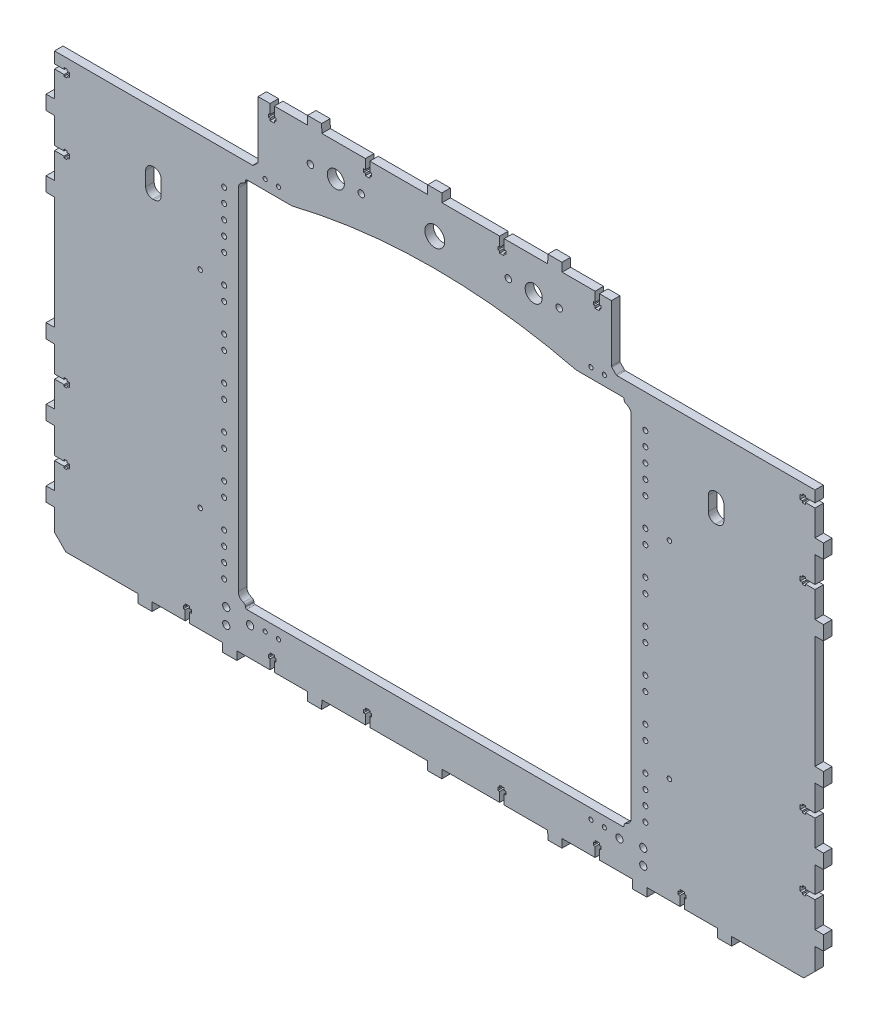
SolidWorks part; units mm, degrees
material "Клен"
ref_plane "Front" through (0, 0, 0) normal (0, 0, 1) x (1, 0, 0)
ref_plane "Top" through (0, 0, 0) normal (0, 1, 0) x (1, 0, 0)
ref_plane "Right" through (0, 0, 0) normal (1, 0, 0) x (0, 0, -1)
sketch "Эскиз1" plane through (0, 0, 0) normal (0, 0, 1) x (1, 0, 0)
  line L0 (1859.5805, 14.5374) -> (1859.5805, 267.5072) construction
  line L1 (1846.6822, 122.5572) -> (1912.7745, 122.5572) construction
  line L2 (1846.6822, 268.5572) -> (1912.7745, 268.5572) construction
  line L3 (1859.5805, 267.5072) -> (1859.5805, 273.1347) construction
  line L6 (1560.5805, 76.7865) -> (1826.5797, 76.7865)
  line L7 (1827.5797, 78.0783) -> (1827.5797, 77.7865)
  line L8 (1832.5805, 332.0072) -> (1832.5797, 84.7865)
  line L9 (1827.5805, 339.0072) -> (1827.5805, 338.7154)
  line L10 (1826.5805, 340.0072) -> (1793.6805, 340.0072)
  line L11 (1560.5805, 340.0072) -> (1592.5638, 340.0072)
  line L13 (1559.5805, 339.0072) -> (1559.5805, 338.7154)
  line L15 (1554.5805, 84.7865) -> (1554.5805, 332.0072)
  line L17 (1559.5805, 78.0783) -> (1559.5805, 77.7865)
  line L18 (1524.5805, 401.0072) -> (1524.5805, 24.1014) construction
  line L19 (1862.5805, 416.6106) -> (1862.5805, 5.7676) construction
  line L20 (1424.5805, 401.0072) -> (1424.5805, 24.1014) construction
  line L21 (1962.5805, 416.6106) -> (1962.5805, 5.7676) construction
  line L22 (1433.5805, 343.0572) -> (1435.0805, 343.0572)
  line L23 (1433.5805, 289.9572) -> (1433.5805, 288.7572)
  line L24 (1433.5805, 149.9572) -> (1433.5805, 148.7572)
  line L25 (1424.5805, 121.4072) -> (1424.5805, 103.0572)
  line L26 (1431.3805, 293.0572) -> (1431.3805, 294.2572)
  line L27 (1431.3805, 154.2572) -> (1433.5805, 154.2572)
  line L28 (1418.5805, 71.5072) -> (1424.5805, 71.4072)
  line L29 (1418.5805, 321.5072) -> (1418.5805, 311.5072)
  line L30 (1418.5805, 311.5072) -> (1424.5805, 311.4072)
  line L31 (1424.5805, 149.9572) -> (1424.5805, 131.6072)
  line L32 (1418.5805, 81.5072) -> (1418.5805, 71.5072)
  line L33 (1433.5805, 338.7572) -> (1431.3805, 338.7572)
  line L34 (1424.5805, 293.0572) -> (1431.3805, 293.0572)
  line L35 (1424.5805, 153.0572) -> (1431.3805, 153.0572)
  line L36 (1433.5805, 103.0572) -> (1435.0805, 103.0572)
  line L37 (1424.5805, 99.9572) -> (1424.5805, 81.6072)
  line L38 (1424.5805, 321.6072) -> (1418.5805, 321.5072)
  line L39 (1433.5805, 293.0572) -> (1435.0805, 293.0572)
  line L40 (1433.5805, 148.7572) -> (1431.3805, 148.7572)
  line L41 (1435.0805, 343.0572) -> (1435.0805, 339.9572)
  line L42 (1431.3805, 289.9572) -> (1424.5805, 289.9572)
  line L43 (1424.5805, 181.6072) -> (1418.5805, 181.5072)
  line L44 (1431.3805, 103.0572) -> (1431.3805, 104.2572)
  line L45 (1435.0805, 103.0572) -> (1435.0805, 99.9572)
  line L46 (1431.3805, 343.0572) -> (1431.3805, 344.2572)
  line L47 (1424.5805, 261.4072) -> (1424.5805, 181.6072)
  line L48 (1433.5805, 153.0572) -> (1435.0805, 153.0572)
  line L49 (1424.5805, 103.0572) -> (1431.3805, 103.0572)
  line L50 (1433.5805, 104.2572) -> (1433.5805, 103.0572)
  line L51 (1424.5805, 311.4072) -> (1424.5805, 293.0572)
  line L52 (1433.5805, 294.2572) -> (1433.5805, 293.0572)
  line L53 (1424.5805, 131.6072) -> (1418.5805, 131.5072)
  line L54 (1431.3805, 338.7572) -> (1431.3805, 339.9572)
  line L55 (1418.5805, 271.5072) -> (1418.5805, 261.5072)
  line L56 (1433.5805, 154.2572) -> (1433.5805, 153.0572)
  line L57 (1433.5805, 98.7572) -> (1431.3805, 98.7572)
  line L58 (1424.5805, 81.6072) -> (1418.5805, 81.5072)
  line L59 (1424.5805, 343.0572) -> (1431.3805, 343.0572)
  line L60 (1431.3805, 339.9572) -> (1424.5805, 339.9572)
  line L61 (1435.0805, 289.9572) -> (1433.5805, 289.9572)
  line L62 (1431.3805, 148.7572) -> (1431.3805, 149.9572)
  line L63 (1435.0805, 339.9572) -> (1433.5805, 339.9572)
  line L64 (1431.3805, 294.2572) -> (1433.5805, 294.2572)
  line L65 (1424.5805, 289.9572) -> (1424.5805, 271.6072)
  line L66 (1433.5805, 99.9572) -> (1433.5805, 98.7572)
  line L67 (1431.3805, 98.7572) -> (1431.3805, 99.9572)
  line L68 (1433.5805, 344.2572) -> (1433.5805, 343.0572)
  line L69 (1424.5805, 271.6072) -> (1418.5805, 271.5072)
  line L70 (1435.0805, 153.0572) -> (1435.0805, 149.9572)
  line L71 (1424.5805, 71.4072) -> (1424.5805, 56.0072)
  line L72 (1431.3805, 344.2572) -> (1433.5805, 344.2572)
  line L73 (1435.0805, 293.0572) -> (1435.0805, 289.9572)
  line L74 (1433.5805, 288.7572) -> (1431.3805, 288.7572)
  line L75 (1418.5805, 131.5072) -> (1418.5805, 121.5072)
  line L76 (1435.0805, 99.9572) -> (1433.5805, 99.9572)
  line L77 (1424.5805, 351.0072) -> (1424.5805, 343.0572)
  line L78 (1418.5805, 171.5072) -> (1424.5805, 171.4072)
  line L79 (1418.5805, 121.5072) -> (1424.5805, 121.4072)
  line L80 (1431.3805, 104.2572) -> (1433.5805, 104.2572)
  line L81 (1431.3805, 288.7572) -> (1431.3805, 289.9572)
  line L82 (1424.5805, 171.4072) -> (1424.5805, 153.0572)
  line L83 (1431.3805, 149.9572) -> (1424.5805, 149.9572)
  line L84 (1433.5805, 339.9572) -> (1433.5805, 338.7572)
  line L85 (1418.5805, 261.5072) -> (1424.5805, 261.4072)
  line L86 (1418.5805, 181.5072) -> (1418.5805, 171.5072)
  line L87 (1431.3805, 99.9572) -> (1424.5805, 99.9572)
  line L88 (1424.5805, 339.9572) -> (1424.5805, 321.6072)
  line L89 (1431.3805, 153.0572) -> (1431.3805, 154.2572)
  line L90 (1435.0805, 149.9572) -> (1433.5805, 149.9572)
  line L91 (1424.5805, 56.0072) -> (1432.5805, 48.0072)
  line L92 (1424.5805, 351.0072) -> (1524.5805, 351.0072)
  line L93 (1432.5805, 48.0072) -> (1483.4805, 48.0072)
  line L94 (1953.5805, 99.9572) -> (1952.0805, 99.9572)
  line L95 (1955.7805, 154.2572) -> (1955.7805, 153.0572)
  line L96 (1953.5805, 289.9572) -> (1952.0805, 289.9572)
  line L97 (1953.5805, 343.0572) -> (1953.5805, 344.2572)
  line L98 (1962.5805, 99.9572) -> (1955.7805, 99.9572)
  line L99 (1955.7805, 153.0572) -> (1962.5805, 153.0572)
  line L100 (1953.5805, 294.2572) -> (1955.7805, 294.2572)
  line L101 (1955.7805, 338.7572) -> (1953.5805, 338.7572)
  line L102 (1953.5805, 103.0572) -> (1953.5805, 104.2572)
  line L103 (1952.0805, 153.0572) -> (1953.5805, 153.0572)
  line L104 (1955.7805, 288.7572) -> (1953.5805, 288.7572)
  line L105 (1962.5805, 321.6072) -> (1962.5805, 339.9572)
  line L106 (1955.7805, 344.2572) -> (1955.7805, 343.0572)
  line L107 (1968.5805, 131.5072) -> (1962.5805, 131.6072)
  line L108 (1962.5805, 149.9572) -> (1955.7805, 149.9572)
  line L109 (1968.5805, 261.5072) -> (1968.5805, 271.5072)
  line L110 (1962.5805, 289.9572) -> (1955.7805, 289.9572)
  line L111 (1955.7805, 343.0572) -> (1962.5805, 343.0572)
  line L112 (1952.0805, 99.9572) -> (1952.0805, 103.0572)
  line L113 (1955.7805, 149.9572) -> (1955.7805, 148.7572)
  line L114 (1952.0805, 293.0572) -> (1953.5805, 293.0572)
  line L115 (1953.5805, 339.9572) -> (1952.0805, 339.9572)
  line L116 (1962.5805, 56.0072) -> (1962.5805, 71.4072)
  line L117 (1955.7805, 103.0572) -> (1962.5805, 103.0572)
  line L118 (1968.5805, 181.5072) -> (1962.5805, 181.6072)
  line L119 (1955.7805, 293.0572) -> (1962.5805, 293.0572)
  line L120 (1953.5805, 344.2572) -> (1955.7805, 344.2572)
  line L121 (1962.5805, 71.4072) -> (1968.5805, 71.5072)
  line L122 (1962.5805, 131.6072) -> (1962.5805, 149.9572)
  line L123 (1968.5805, 171.5072) -> (1968.5805, 181.5072)
  line L124 (1968.5805, 271.5072) -> (1962.5805, 271.6072)
  line L125 (1953.5805, 104.2572) -> (1955.7805, 104.2572)
  line L126 (1953.5805, 153.0572) -> (1953.5805, 154.2572)
  line L127 (1953.5805, 293.0572) -> (1953.5805, 294.2572)
  line L128 (1953.5805, 98.7572) -> (1953.5805, 99.9572)
  line L129 (1962.5805, 121.4072) -> (1968.5805, 121.5072)
  line L130 (1962.5805, 261.4072) -> (1968.5805, 261.5072)
  line L131 (1952.0805, 289.9572) -> (1952.0805, 293.0572)
  line L132 (1952.0805, 343.0572) -> (1953.5805, 343.0572)
  line L133 (1968.5805, 81.5072) -> (1962.5805, 81.6072)
  line L134 (1955.7805, 148.7572) -> (1953.5805, 148.7572)
  line L135 (1962.5805, 293.0572) -> (1962.5805, 311.4072)
  line L136 (1952.0805, 339.9572) -> (1952.0805, 343.0572)
  line L137 (1955.7805, 98.7572) -> (1953.5805, 98.7572)
  line L138 (1962.5805, 103.0572) -> (1962.5805, 121.4072)
  line L139 (1962.5805, 181.6072) -> (1962.5805, 261.4072)
  line L140 (1962.5805, 311.4072) -> (1968.5805, 311.5072)
  line L141 (1952.0805, 103.0572) -> (1953.5805, 103.0572)
  line L142 (1955.7805, 294.2572) -> (1955.7805, 293.0572)
  line L143 (1962.5805, 339.9572) -> (1955.7805, 339.9572)
  line L144 (1955.7805, 104.2572) -> (1955.7805, 103.0572)
  line L145 (1953.5805, 154.2572) -> (1955.7805, 154.2572)
  line L146 (1955.7805, 289.9572) -> (1955.7805, 288.7572)
  line L147 (1968.5805, 121.5072) -> (1968.5805, 131.5072)
  line L148 (1953.5805, 288.7572) -> (1953.5805, 289.9572)
  line L149 (1955.7805, 339.9572) -> (1955.7805, 338.7572)
  line L150 (1954.5805, 48.0072) -> (1962.5805, 56.0072)
  line L151 (1962.5805, 81.6072) -> (1962.5805, 99.9572)
  line L152 (1953.5805, 149.9572) -> (1952.0805, 149.9572)
  line L153 (1962.5805, 171.4072) -> (1968.5805, 171.5072)
  line L154 (1968.5805, 311.5072) -> (1968.5805, 321.5072)
  line L155 (1955.7805, 99.9572) -> (1955.7805, 98.7572)
  line L156 (1952.0805, 149.9572) -> (1952.0805, 153.0572)
  line L157 (1962.5805, 271.6072) -> (1962.5805, 289.9572)
  line L158 (1968.5805, 321.5072) -> (1962.5805, 321.6072)
  line L159 (1962.5805, 343.0572) -> (1962.5805, 351.0072)
  line L160 (1968.5805, 71.5072) -> (1968.5805, 81.5072)
  line L161 (1953.5805, 148.7572) -> (1953.5805, 149.9572)
  line L162 (1962.5805, 153.0572) -> (1962.5805, 171.4072)
  line L163 (1953.5805, 338.7572) -> (1953.5805, 339.9572)
  line L164 (1862.5805, 351.0072) -> (1962.5805, 351.0072)
  line L165 (1954.5805, 48.0072) -> (1903.6805, 48.0072)
  line L166 (1325.5433, 339.9572) -> (1983.9894, 339.9572) construction
  line L167 (1983.9894, 304.9572) -> (1788.8393, 304.9572) construction
  line L168 (1892.5805, 416.6106) -> (1892.5805, 273.8352) construction
  line L169 (1693.5805, 412.8647) -> (1693.5805, 297.5072) construction
  line L170 (1892.0805, 314.9572) -> (1893.0805, 314.9572)
  line L171 (1887.0805, 309.9572) -> (1887.0805, 299.9572)
  line L172 (1892.0805, 294.9572) -> (1893.0805, 294.9572)
  line L173 (1898.0805, 309.9572) -> (1898.0805, 299.9572)
  line L174 (1887.0805, 314.9572) -> (1898.0805, 294.9572) construction
  line L175 (1887.0805, 294.9572) -> (1898.0805, 314.9572) construction
  line L176 (1495.0805, 294.9572) -> (1494.0805, 294.9572)
  line L177 (1489.0805, 309.9572) -> (1489.0805, 299.9572)
  line L178 (1495.0805, 314.9572) -> (1494.0805, 314.9572)
  line L179 (1500.0805, 309.9572) -> (1500.0805, 299.9572)
  line L180 (1893.4805, 48.0072) -> (1893.5805, 42.0072)
  line L181 (1867.0305, 58.5072) -> (1870.1305, 58.5072)
  line L182 (1903.5805, 42.0072) -> (1903.6805, 48.0072)
  line L183 (1867.0305, 54.8072) -> (1865.8305, 54.8072)
  line L184 (1870.1305, 58.5072) -> (1870.1305, 57.0072)
  line L185 (1871.3305, 54.8072) -> (1870.1305, 54.8072)
  line L186 (1865.8305, 57.0072) -> (1867.0305, 57.0072)
  line L187 (1871.3305, 57.0072) -> (1871.3305, 54.8072)
  line L188 (1867.0305, 48.0072) -> (1867.0305, 54.8072)
  line L189 (1870.1305, 57.0072) -> (1871.3305, 57.0072)
  line L190 (1870.1305, 54.8072) -> (1870.1305, 48.0072)
  line L192 (1865.8305, 54.8072) -> (1865.8305, 57.0072)
  line L193 (1893.5805, 42.0072) -> (1903.5805, 42.0072)
  line L194 (1867.0305, 57.0072) -> (1867.0305, 58.5072)
  line L195 (1867.0305, 48.0072) -> (1854.5805, 48.0072)
  line L196 (1893.4805, 48.0072) -> (1870.1305, 48.0072)
  line L197 (1493.5805, 42.0072) -> (1493.6805, 48.0072)
  line L198 (1521.3305, 57.0072) -> (1521.3305, 54.8072)
  line L199 (1517.0305, 48.0072) -> (1517.0305, 54.8072)
  line L200 (1483.5805, 42.0072) -> (1493.5805, 42.0072)
  line L201 (1515.8305, 57.0072) -> (1517.0305, 57.0072)
  line L202 (1521.3305, 54.8072) -> (1520.1305, 54.8072)
  line L203 (1483.4805, 48.0072) -> (1483.5805, 42.0072)
  line L204 (1517.0305, 57.0072) -> (1517.0305, 58.5072)
  line L205 (1517.0305, 58.5072) -> (1520.1305, 58.5072)
  line L206 (1517.0305, 54.8072) -> (1515.8305, 54.8072)
  line L207 (1520.1305, 54.8072) -> (1520.1305, 48.0072)
  line L209 (1520.1305, 58.5072) -> (1520.1305, 57.0072)
  line L210 (1520.1305, 57.0072) -> (1521.3305, 57.0072)
  line L211 (1515.8305, 54.8072) -> (1515.8305, 57.0072)
  line L212 (1520.1305, 48.0072) -> (1532.5805, 48.0072)
  line L213 (1493.6805, 48.0072) -> (1517.0305, 48.0072)
  line L552 (1568.2876, 354.2143) -> (1565.3733, 351.3001)
  line L553 (1564.6662, 351.0072) -> (1524.5805, 351.0072)
  line L624 (1532.5805, 48.0072) -> (1543.4805, 48.0072)
  line L625 (1543.4805, 48.0072) -> (1543.5805, 42.0072)
  line L626 (1543.5805, 42.0072) -> (1553.5805, 42.0072)
  line L627 (1553.5805, 42.0072) -> (1553.6805, 48.0072)
  line L628 (1553.6805, 48.0072) -> (1577.0305, 48.0072)
  line L629 (1577.0305, 48.0072) -> (1577.0305, 54.8072)
  line L630 (1577.0305, 54.8072) -> (1575.8305, 54.8072)
  line L631 (1575.8305, 54.8072) -> (1575.8305, 57.0072)
  line L632 (1575.8305, 57.0072) -> (1577.0305, 57.0072)
  line L633 (1577.0305, 57.0072) -> (1577.0305, 58.5072)
  line L634 (1577.0305, 58.5072) -> (1580.1305, 58.5072)
  line L635 (1580.1305, 58.5072) -> (1580.1305, 57.0072)
  line L636 (1580.1305, 57.0072) -> (1581.3305, 57.0072)
  line L637 (1581.3305, 57.0072) -> (1581.3305, 54.8072)
  line L638 (1581.3305, 54.8072) -> (1580.1305, 54.8072)
  line L639 (1580.1305, 54.8072) -> (1580.1305, 48.0072)
  line L640 (1580.1305, 48.0072) -> (1603.4805, 48.0072)
  line L641 (1603.4805, 48.0072) -> (1603.5805, 42.0072)
  line L642 (1603.5805, 42.0072) -> (1613.5805, 42.0072)
  line L643 (1613.5805, 42.0072) -> (1613.6805, 48.0072)
  line L644 (1613.6805, 48.0072) -> (1644.5305, 48.0072)
  line L645 (1644.5305, 48.0072) -> (1644.5305, 54.8072)
  line L646 (1644.5305, 54.8072) -> (1643.3305, 54.8072)
  line L647 (1643.3305, 54.8072) -> (1643.3305, 57.0072)
  line L648 (1643.3305, 57.0072) -> (1644.5305, 57.0072)
  line L649 (1644.5305, 57.0072) -> (1644.5305, 58.5072)
  line L650 (1644.5305, 58.5072) -> (1647.6305, 58.5072)
  line L651 (1647.6305, 58.5072) -> (1647.6305, 57.0072)
  line L652 (1647.6305, 57.0072) -> (1648.8305, 57.0072)
  line L653 (1648.8305, 57.0072) -> (1648.8305, 54.8072)
  line L654 (1648.8305, 54.8072) -> (1647.6305, 54.8072)
  line L655 (1647.6305, 54.8072) -> (1647.6305, 48.0072)
  line L656 (1647.6305, 48.0072) -> (1688.4805, 48.0072)
  line L657 (1688.4805, 48.0072) -> (1688.5805, 42.0072)
  line L658 (1688.5805, 42.0072) -> (1698.5805, 42.0072)
  line L659 (1698.5805, 42.0072) -> (1698.6805, 48.0072)
  line L660 (1698.6805, 48.0072) -> (1739.5305, 48.0072)
  line L661 (1739.5305, 48.0072) -> (1739.5305, 54.8072)
  line L662 (1739.5305, 54.8072) -> (1738.3305, 54.8072)
  line L663 (1738.3305, 54.8072) -> (1738.3305, 57.0072)
  line L664 (1738.3305, 57.0072) -> (1739.5305, 57.0072)
  line L665 (1739.5305, 57.0072) -> (1739.5305, 58.5072)
  line L666 (1739.5305, 58.5072) -> (1742.6305, 58.5072)
  line L667 (1742.6305, 58.5072) -> (1742.6305, 57.0072)
  line L668 (1742.6305, 57.0072) -> (1743.8305, 57.0072)
  line L669 (1743.8305, 57.0072) -> (1743.8305, 54.8072)
  line L670 (1743.8305, 54.8072) -> (1742.6305, 54.8072)
  line L671 (1742.6305, 54.8072) -> (1742.6305, 48.0072)
  line L672 (1742.6305, 48.0072) -> (1773.4805, 48.0072)
  line L673 (1773.4805, 48.0072) -> (1773.5805, 42.0072)
  line L674 (1773.5805, 42.0072) -> (1783.5805, 42.0072)
  line L675 (1783.5805, 42.0072) -> (1783.6805, 48.0072)
  line L676 (1783.6805, 48.0072) -> (1807.0305, 48.0072)
  line L677 (1807.0305, 48.0072) -> (1807.0305, 54.8072)
  line L678 (1807.0305, 54.8072) -> (1805.8305, 54.8072)
  line L679 (1805.8305, 54.8072) -> (1805.8305, 57.0072)
  line L680 (1805.8305, 57.0072) -> (1807.0305, 57.0072)
  line L681 (1807.0305, 57.0072) -> (1807.0305, 58.5072)
  line L682 (1807.0305, 58.5072) -> (1810.1305, 58.5072)
  line L683 (1810.1305, 58.5072) -> (1810.1305, 57.0072)
  line L684 (1810.1305, 57.0072) -> (1811.3305, 57.0072)
  line L685 (1811.3305, 57.0072) -> (1811.3305, 54.8072)
  line L686 (1811.3305, 54.8072) -> (1810.1305, 54.8072)
  line L687 (1810.1305, 54.8072) -> (1810.1305, 48.0072)
  line L688 (1810.1305, 48.0072) -> (1833.4805, 48.0072)
  line L689 (1833.4805, 48.0072) -> (1833.5805, 42.0072)
  line L690 (1833.5805, 42.0072) -> (1843.5805, 42.0072)
  line L691 (1843.5805, 42.0072) -> (1843.6805, 48.0072)
  line L692 (1843.6805, 48.0072) -> (1854.5805, 48.0072)
  line L763 (1862.5805, 351.0072) -> (1822.4947, 351.0072)
  line L764 (1821.7876, 351.3001) -> (1818.8733, 354.2143)
  line L765 (1818.5805, 354.9215) -> (1818.5805, 395.0072)
  line L766 (1818.5805, 395.0072) -> (1810.1305, 395.0072)
  line L767 (1810.1305, 395.0072) -> (1810.1305, 388.2072)
  line L768 (1810.1305, 388.2072) -> (1811.3305, 388.2072)
  line L769 (1811.3305, 388.2072) -> (1811.3305, 386.0072)
  line L770 (1811.3305, 386.0072) -> (1810.1305, 386.0072)
  line L771 (1810.1305, 386.0072) -> (1810.1305, 384.5072)
  line L772 (1810.1305, 384.5072) -> (1807.0305, 384.5072)
  line L773 (1807.0305, 384.5072) -> (1807.0305, 386.0072)
  line L774 (1807.0305, 386.0072) -> (1805.8305, 386.0072)
  line L775 (1805.8305, 386.0072) -> (1805.8305, 388.2072)
  line L776 (1805.8305, 388.2072) -> (1807.0305, 388.2072)
  line L777 (1807.0305, 388.2072) -> (1807.0305, 395.0072)
  line L778 (1807.0305, 395.0072) -> (1783.6805, 395.0072)
  line L779 (1783.6805, 395.0072) -> (1783.5805, 401.0072)
  line L780 (1783.5805, 401.0072) -> (1773.5805, 401.0072)
  line L781 (1773.5805, 401.0072) -> (1773.4805, 395.0072)
  line L782 (1773.4805, 395.0072) -> (1742.6305, 395.0072)
  line L783 (1742.6305, 395.0072) -> (1742.6305, 388.2072)
  line L784 (1742.6305, 388.2072) -> (1743.8305, 388.2072)
  line L785 (1743.8305, 388.2072) -> (1743.8305, 386.0072)
  line L786 (1743.8305, 386.0072) -> (1742.6305, 386.0072)
  line L787 (1742.6305, 386.0072) -> (1742.6305, 384.5072)
  line L788 (1742.6305, 384.5072) -> (1739.5305, 384.5072)
  line L789 (1739.5305, 384.5072) -> (1739.5305, 386.0072)
  line L790 (1739.5305, 386.0072) -> (1738.3305, 386.0072)
  line L791 (1738.3305, 386.0072) -> (1738.3305, 388.2072)
  line L792 (1738.3305, 388.2072) -> (1739.5305, 388.2072)
  line L793 (1739.5305, 388.2072) -> (1739.5305, 395.0072)
  line L794 (1739.5305, 395.0072) -> (1698.6805, 395.0072)
  line L795 (1698.6805, 395.0072) -> (1698.5805, 401.0072)
  line L796 (1698.5805, 401.0072) -> (1688.5805, 401.0072)
  line L797 (1688.5805, 401.0072) -> (1688.4805, 395.0072)
  line L798 (1688.4805, 395.0072) -> (1647.6305, 395.0072)
  line L799 (1647.6305, 395.0072) -> (1647.6305, 388.2072)
  line L800 (1647.6305, 388.2072) -> (1648.8305, 388.2072)
  line L801 (1648.8305, 388.2072) -> (1648.8305, 386.0072)
  line L802 (1648.8305, 386.0072) -> (1647.6305, 386.0072)
  line L803 (1647.6305, 386.0072) -> (1647.6305, 384.5072)
  line L804 (1647.6305, 384.5072) -> (1644.5305, 384.5072)
  line L805 (1644.5305, 384.5072) -> (1644.5305, 386.0072)
  line L806 (1644.5305, 386.0072) -> (1643.3305, 386.0072)
  line L807 (1643.3305, 386.0072) -> (1643.3305, 388.2072)
  line L808 (1643.3305, 388.2072) -> (1644.5305, 388.2072)
  line L809 (1644.5305, 388.2072) -> (1644.5305, 395.0072)
  line L810 (1644.5305, 395.0072) -> (1613.6805, 395.0072)
  line L811 (1613.6805, 395.0072) -> (1613.5805, 401.0072)
  line L812 (1613.5805, 401.0072) -> (1603.5805, 401.0072)
  line L813 (1603.5805, 401.0072) -> (1603.4805, 395.0072)
  line L814 (1603.4805, 395.0072) -> (1580.1305, 395.0072)
  line L815 (1580.1305, 395.0072) -> (1580.1305, 388.2072)
  line L816 (1580.1305, 388.2072) -> (1581.3305, 388.2072)
  line L817 (1581.3305, 388.2072) -> (1581.3305, 386.0072)
  line L818 (1581.3305, 386.0072) -> (1580.1305, 386.0072)
  line L819 (1580.1305, 386.0072) -> (1580.1305, 384.5072)
  line L820 (1580.1305, 384.5072) -> (1577.0305, 384.5072)
  line L821 (1577.0305, 384.5072) -> (1577.0305, 386.0072)
  line L822 (1577.0305, 386.0072) -> (1575.8305, 386.0072)
  line L823 (1575.8305, 386.0072) -> (1575.8305, 388.2072)
  line L824 (1575.8305, 388.2072) -> (1577.0305, 388.2072)
  line L825 (1577.0305, 388.2072) -> (1577.0305, 395.0072)
  line L826 (1577.0305, 395.0072) -> (1568.5805, 395.0072)
  line L827 (1568.5805, 395.0072) -> (1568.5805, 354.9215)
  circle A0 centre (1859.5805, 268.5572) radius 1.6
  circle A1 centre (1859.5805, 122.5572) radius 1.6
  circle A2 centre (1527.5805, 268.5572) radius 1.6
  circle A3 centre (1527.5805, 122.5572) radius 1.6
  arc A4 (1893.0805, 294.9572) -> (1898.0805, 299.9572) centre (1893.0805, 299.9572) ccw
  arc A5 (1887.0805, 299.9572) -> (1892.0805, 294.9572) centre (1892.0805, 299.9572) ccw
  arc A6 (1893.0805, 314.9572) -> (1898.0805, 309.9572) centre (1893.0805, 309.9572) cw
  arc A7 (1892.0805, 314.9572) -> (1887.0805, 309.9572) centre (1892.0805, 309.9572) ccw
  arc A8 (1568.2876, 354.2143) -> (1568.5805, 354.9215) centre (1567.5805, 354.9215) ccw
  arc A9 (1564.6662, 351.0072) -> (1565.3733, 351.3001) centre (1564.6662, 352.0072) ccw
  arc A10 (1821.7876, 351.3001) -> (1822.4947, 351.0072) centre (1822.4947, 352.0072) ccw
  arc A11 (1818.5805, 354.9215) -> (1818.8733, 354.2143) centre (1819.5805, 354.9215) ccw
  circle A28 centre (1544.5805, 177.5072) radius 1.75
  circle A29 centre (1544.5805, 147.5072) radius 1.75
  circle A30 centre (1544.5805, 137.5072) radius 1.75
  circle A31 centre (1544.5805, 117.5072) radius 1.75
  circle A32 centre (1544.5805, 107.5072) radius 1.75
  circle A33 centre (1544.5805, 97.5072) radius 1.75
  circle A34 centre (1544.5805, 87.5072) radius 1.75
  circle A35 centre (1546.0805, 71.0072) radius 2.55
  circle A36 centre (1546.0805, 60.0072) radius 2.55
  circle A37 centre (1544.5805, 197.5072) radius 1.75
  circle A38 centre (1544.5805, 207.5072) radius 1.75
  circle A39 centre (1544.5805, 227.5072) radius 1.75
  circle A40 centre (1544.5805, 237.5072) radius 1.75
  circle A41 centre (1544.5805, 257.5072) radius 1.75
  circle A42 centre (1544.5805, 267.5072) radius 1.75
  circle A43 centre (1544.5805, 287.5072) radius 1.75
  circle A44 centre (1544.5805, 297.5072) radius 1.75
  circle A45 centre (1544.5805, 307.5072) radius 1.75
  circle A46 centre (1544.5805, 317.5072) radius 1.75
  circle A47 centre (1544.5805, 327.5072) radius 1.75
  circle A87 centre (1573.5805, 347.0072) radius 1.5
  circle A88 centre (1583.0805, 347.0072) radius 1.5
  circle A89 centre (1605.5805, 372.0072) radius 2.3
  circle A90 centre (1623.5805, 372.0072) radius 6.05
  circle A91 centre (1641.5805, 372.0072) radius 2.3
  circle A92 centre (1693.5805, 372.0072) radius 7
  circle A93 centre (1745.5805, 372.0072) radius 2.3
  circle A94 centre (1763.5805, 372.0072) radius 6.05
  circle A95 centre (1781.5805, 372.0072) radius 2.3
  circle A96 centre (1804.0805, 347.0072) radius 1.5
  circle A97 centre (1813.5805, 347.0072) radius 1.5
  circle A98 centre (1842.5805, 327.5072) radius 1.75
  circle A99 centre (1842.5805, 317.5072) radius 1.75
  circle A100 centre (1842.5805, 307.5072) radius 1.75
  circle A101 centre (1842.5805, 297.5072) radius 1.75
  circle A102 centre (1842.5805, 287.5072) radius 1.75
  circle A103 centre (1842.5805, 267.5072) radius 1.75
  circle A104 centre (1842.5805, 257.5072) radius 1.75
  circle A105 centre (1842.5805, 237.5072) radius 1.75
  circle A106 centre (1842.5805, 227.5072) radius 1.75
  circle A107 centre (1842.5805, 207.5072) radius 1.75
  circle A108 centre (1842.5805, 197.5072) radius 1.75
  circle A109 centre (1842.5805, 177.5072) radius 1.75
  circle A110 centre (1842.5805, 167.5072) radius 1.75
  circle A111 centre (1842.5805, 147.5072) radius 1.75
  circle A112 centre (1842.5805, 137.5072) radius 1.75
  circle A113 centre (1842.5805, 117.5072) radius 1.75
  circle A114 centre (1842.5805, 107.5072) radius 1.75
  circle A115 centre (1842.5805, 97.5072) radius 1.75
  circle A116 centre (1842.5805, 87.5072) radius 1.75
  circle A117 centre (1841.0805, 71.0072) radius 2.55
  circle A118 centre (1841.0805, 60.0072) radius 2.55
  circle A119 centre (1824.2277, 68.2968) radius 2.55
  circle A120 centre (1813.5805, 69.7865) radius 1.5
  circle A121 centre (1804.0805, 69.7865) radius 1.5
  circle A122 centre (1583.0805, 69.7865) radius 1.5
  circle A123 centre (1573.5805, 69.7865) radius 1.5
  circle A124 centre (1562.9305, 68.2968) radius 2.55
  circle A125 centre (1544.5805, 167.5072) radius 1.75
  arc A133 (1826.5797, 76.7865) -> (1827.5797, 77.7865) centre (1826.5797, 77.7865) ccw
  arc A134 (1829.0083, 79.995) -> (1827.5797, 78.0783) centre (1829.5797, 78.0783) ccw
  arc A135 (1829.0083, 79.995) -> (1832.5797, 84.7865) centre (1827.5797, 84.7865) ccw
  arc A136 (1832.5805, 332.0072) -> (1829.009, 336.7988) centre (1827.5805, 332.0072) ccw
  arc A137 (1827.5805, 338.7154) -> (1829.009, 336.7988) centre (1829.5805, 338.7154) ccw
  arc A138 (1827.5805, 339.0072) -> (1826.5805, 340.0072) centre (1826.5805, 339.0072) ccw
  arc A139 (1793.6805, 340.0072) -> (1592.5638, 340.0072) centre (1693.1221, -70.0562) ccw
  arc A141 (1560.5805, 340.0072) -> (1559.5805, 339.0072) centre (1560.5805, 339.0072) ccw
  arc A143 (1558.1519, 336.7988) -> (1559.5805, 338.7154) centre (1557.5805, 338.7154) ccw
  arc A145 (1558.1519, 336.7988) -> (1554.5805, 332.0072) centre (1559.5805, 332.0072) ccw
  arc A147 (1559.5805, 77.7865) -> (1560.5805, 76.7865) centre (1560.5805, 77.7865) ccw
  arc A149 (1554.5805, 84.7865) -> (1558.1519, 79.995) centre (1559.5805, 84.7865) ccw
  arc A151 (1559.5805, 78.0783) -> (1558.1519, 79.995) centre (1557.5805, 78.0783) ccw
  arc A152 (1494.0805, 294.9572) -> (1489.0805, 299.9572) centre (1494.0805, 299.9572) cw
  arc A153 (1494.0805, 314.9572) -> (1489.0805, 309.9572) centre (1494.0805, 309.9572) ccw
  arc A154 (1500.0805, 299.9572) -> (1495.0805, 294.9572) centre (1495.0805, 299.9572) cw
  arc A155 (1495.0805, 314.9572) -> (1500.0805, 309.9572) centre (1495.0805, 309.9572) cw
  point P18 (1892.5805, 304.9572)
  dimension "D7" = 5
  dimension "D11" = 3.2
  dimension "D12" = 3.2
  dimension "D2" = 100
  dimension "D3" = 100
  dimension "D4" = 30
  dimension "D1" = 35
  dimension "D5" = 11
  dimension "D6" = 20
  dimension "D8" = 3
  dimension "D9" = 74.55
  dimension "D10" = 146
extrude "Бобышка-Вытянуть1" add sketch "Эскиз1" along normal blind 6
